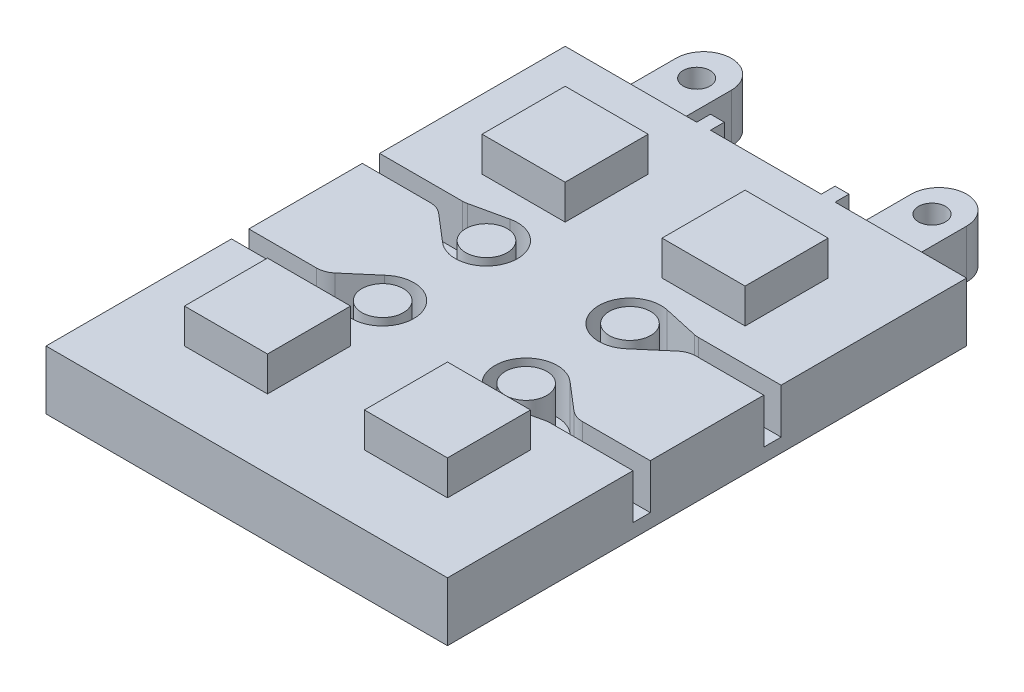
SolidWorks part; units mm, degrees
ref_plane "Front Plane" through (0, 0, 0) normal (0, 0, 1) x (1, 0, 0)
ref_plane "Top Plane" through (0, 0, 0) normal (0, 1, 0) x (1, 0, 0)
ref_plane "Right Plane" through (0, 0, 0) normal (1, 0, 0) x (0, 0, -1)
sketch "Sketch1" plane through (0, 0, 0) normal (0, 1, 0) x (1, 0, 0)
  line L1 (-57.7343, 34.4056) -> (0.2657, 34.4056)
  line L2 (-57.7343, 34.4056) -> (-57.7343, -40.5944)
  line L3 (-57.7343, -40.5944) -> (0.2657, -40.5944)
  line L4 (0.2657, 34.4056) -> (0.2657, -40.5944)
  dimension "D1" = 58
  dimension "D2" = 75
extrude "Boss-Extrude1" add sketch "Sketch1" along normal blind 8.5
sketch "Sketch4" plane through (0, 8.5, 0) normal (0, 1, 0) x (1, 0, 0)
  line L11 (0.2657, 34.4056) -> (-57.7343, 34.4056) construction
  line L12 (-57.7343, -3.0944) -> (18.5332, -3.0944) construction
  line L13 (-57.7343, 34.4056) -> (-57.7343, -40.5944) construction
  line L14 (-28.7343, 34.4056) -> (-28.7343, -40.5944) construction
  line L15 (-57.7343, -40.5944) -> (0.2657, -40.5944) construction
  line B0 (-57.7343, 7.6056) -> (-57.7343, 5.1056)
  line B1 (-57.7343, 7.6056) -> (-45.7867, 7.6056)
  line B2 (-45.138, 7.6766) -> (-40.0697, 8.7991)
  line B3 (-57.7343, 5.1056) -> (-47.9373, 5.1056)
  line B4 (-45.9858, 4.3841) -> (-42.1311, 1.0827)
  circle B5 centre (-39.0966, 4.4056) radius 3
  arc B6 (-42.1311, 1.0827) -> (-40.0697, 8.7991) centre (-39.0966, 4.4056) ccw
  arc B7 (-45.7867, 7.6056) -> (-45.138, 7.6766) centre (-45.7867, 10.6056) ccw
  arc B8 (-47.9373, 5.1056) -> (-45.9858, 4.3841) centre (-47.9373, 2.1056) cw
  line B9 (-57.7343, -13.7944) -> (-57.7343, -11.2944)
  line B10 (-57.7343, -13.7944) -> (-45.7867, -13.7944)
  line B11 (-45.138, -13.8654) -> (-40.0697, -14.9879)
  line B12 (-57.7343, -11.2944) -> (-47.9373, -11.2944)
  line B13 (-45.9858, -10.5729) -> (-42.1311, -7.2715)
  circle B14 centre (-39.0966, -10.5944) radius 3
  arc B15 (-42.1311, -7.2715) -> (-40.0697, -14.9879) centre (-39.0966, -10.5944) cw
  arc B16 (-45.7867, -13.7944) -> (-45.138, -13.8654) centre (-45.7867, -16.7944) cw
  arc B17 (-47.9373, -11.2944) -> (-45.9858, -10.5729) centre (-47.9373, -8.2944) ccw
  line B18 (0.2657, -13.7944) -> (0.2657, -11.2944)
  line B19 (0.2657, -13.7944) -> (-11.6818, -13.7944)
  line B20 (-12.3306, -13.8654) -> (-17.3989, -14.9879)
  line B21 (0.2657, -11.2944) -> (-9.5312, -11.2944)
  line B22 (-11.4827, -10.5729) -> (-15.3374, -7.2715)
  circle B23 centre (-18.372, -10.5944) radius 3
  arc B24 (-15.3374, -7.2715) -> (-17.3989, -14.9879) centre (-18.372, -10.5944) ccw
  arc B25 (-11.6818, -13.7944) -> (-12.3306, -13.8654) centre (-11.6818, -16.7944) ccw
  arc B26 (-9.5312, -11.2944) -> (-11.4827, -10.5729) centre (-9.5312, -8.2944) cw
  line B27 (0.2657, 7.6056) -> (0.2657, 5.1056)
  line B28 (0.2657, 7.6056) -> (-11.6818, 7.6056)
  line B29 (-12.3306, 7.6766) -> (-17.3989, 8.7991)
  line B30 (0.2657, 5.1056) -> (-9.5312, 5.1056)
  line B31 (-11.4827, 4.3841) -> (-15.3374, 1.0827)
  circle B32 centre (-18.372, 4.4056) radius 3
  arc B33 (-15.3374, 1.0827) -> (-17.3989, 8.7991) centre (-18.372, 4.4056) cw
  arc B34 (-11.6818, 7.6056) -> (-12.3306, 7.6766) centre (-11.6818, 10.6056) cw
  arc B35 (-9.5312, 5.1056) -> (-11.4827, 4.3841) centre (-9.5312, 2.1056) ccw
  dimension "D1" = 30
sketch_block_instance "Block1-1"
sketch_block "Block1" parameters "D2"=3, "D1"=2.5
sketch_block_instance "Block1-2"
sketch_block_instance "Block1-3"
sketch_block_instance "Block1-4"
extrude "Cut-Extrude1" cut sketch "Sketch4" against normal blind 6.5
sketch "Sketch5" plane through (0, 8.5, 0) normal (0, 1, 0) x (1, 0, 0)
  line L0 (0.2657, 34.4056) -> (-57.7343, 34.4056) construction
  line L1 (-47.7343, 24.4056) -> (-35.7343, 24.4056)
  line L2 (-47.7343, 24.4056) -> (-47.7343, 12.4056)
  line L3 (-47.7343, 12.4056) -> (-35.7343, 12.4056)
  line L4 (-35.7343, 24.4056) -> (-35.7343, 12.4056)
  line L9 (-57.7343, 34.4056) -> (-57.7343, 7.6056) construction
  line L10 (-28.7343, 34.4056) -> (-28.7343, -40.5944) construction
  line L11 (-57.7343, -40.5944) -> (0.2657, -40.5944) construction
  line L12 (-57.7343, -3.0944) -> (0.2657, -3.0944) construction
  line L13 (-57.7343, 5.1056) -> (-57.7343, -11.2944) construction
  line L14 (0.2657, -11.2944) -> (0.2657, 5.1056) construction
  line L15 (-21.7343, 24.4056) -> (-21.7343, 12.4056)
  line L16 (-9.7343, 12.4056) -> (-21.7343, 12.4056)
  line L17 (-9.7343, 24.4056) -> (-9.7343, 12.4056)
  line L18 (-9.7343, 24.4056) -> (-21.7343, 24.4056)
  line L19 (-9.7343, -30.5944) -> (-21.7343, -30.5944)
  line L20 (-9.7343, -30.5944) -> (-9.7343, -18.5944)
  line L21 (-9.7343, -18.5944) -> (-21.7343, -18.5944)
  line L22 (-21.7343, -30.5944) -> (-21.7343, -18.5944)
  line L23 (-35.7343, -30.5944) -> (-35.7343, -18.5944)
  line L24 (-47.7343, -18.5944) -> (-35.7343, -18.5944)
  line L25 (-47.7343, -30.5944) -> (-47.7343, -18.5944)
  line L26 (-47.7343, -30.5944) -> (-35.7343, -30.5944)
  dimension "D1" = 12
  dimension "D2" = 12
  dimension "D3" = 10
  dimension "D4" = 10
extrude "Boss-Extrude2" add sketch "Sketch5" along normal blind 5
sketch "Sketch7" plane through (0, 0, -34.4056) normal (0, 0, -1) x (-1, 0, 0)
  line L0 (-0.2657, 0) -> (57.7343, 0) construction
  line L1 (49.7343, 0) -> (41.7343, 0)
  line L2 (49.7343, 0) -> (49.7343, 7)
  line L3 (49.7343, 7) -> (41.7343, 7)
  line L4 (41.7343, 0) -> (41.7343, 7)
  line L5 (57.7343, 8.5) -> (57.7343, 0) construction
  line L6 (15.7343, 0) -> (7.7343, 0)
  line L7 (15.7343, 0) -> (15.7343, 7)
  line L8 (15.7343, 7) -> (7.7343, 7)
  line L9 (7.7343, 0) -> (7.7343, 7)
  point P10 (49.7343, 3.5)
  dimension "D1" = 7
  dimension "D2" = 8
  dimension "D3" = 8
  dimension "D4" = 26
  dimension "D5" = 8
sketch "Sketch8" plane through (0, 0, -34.4056) normal (0, 0, -1) x (-1, 0, 0)
  line L0 (-0.2657, 0) -> (57.7343, 0) construction
  line L1 (38.7343, 0) -> (36.7343, 0)
  line L2 (38.7343, 0) -> (38.7343, 8.5)
  line L3 (38.7343, 8.5) -> (36.7343, 8.5)
  line L4 (36.7343, 0) -> (36.7343, 8.5)
  line L5 (-0.2657, 8.5) -> (57.7343, 8.5) construction
  line L6 (41.7343, 0) -> (41.7343, 7) construction
  line L7 (20.7343, 0) -> (18.7343, 0)
  line L8 (20.7343, 0) -> (20.7343, 8.5)
  line L9 (20.7343, 8.5) -> (18.7343, 8.5)
  line L10 (18.7343, 0) -> (18.7343, 8.5)
  line L11 (15.7343, 0) -> (15.7343, 7) construction
  dimension "D1" = 2
  dimension "D2" = 2
  dimension "D3" = 3
  dimension "D4" = 3
extrude "Boss-Extrude3" add sketch "Sketch8" along normal blind 2
extrude "Boss-Extrude4" add sketch "Sketch7" along normal blind 12
sketch "Sketch9" plane through (0, 0, 0) normal (0, -1, 0) x (-1, 0, 0)
  line L0 (7.7343, 46.4056) -> (15.7343, 46.4056) construction
  line L2 (7.7343, 46.4056) -> (7.7343, 34.4056) construction
  line L3 (41.7343, 46.4056) -> (41.7343, 34.4056) construction
  circle A0 centre (11.7343, 41.4056) radius 1.95
  circle A1 centre (45.7343, 41.4056) radius 1.95
  dimension "D1" = 5
  dimension "D2" = 4
  dimension "D3" = 4
extrude "Cut-Extrude2" cut sketch "Sketch9" against normal up to surface (7 mm away) up to face at (-45.7343, 7, -40.4056)
fillet "Fillet1" radius 4 4 edges at (-7.7343, 3.5, -46.4056) (-15.7343, 3.5, -46.4056) (-49.7343, 3.5, -46.4056) (-41.7343, 3.5, -46.4056)
